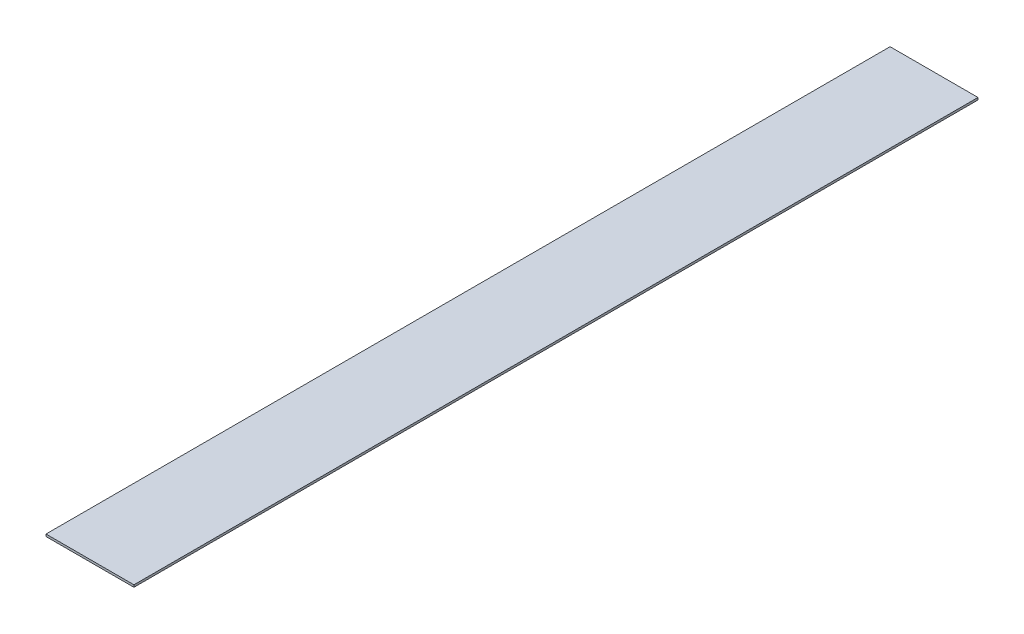
SolidWorks part; units mm, degrees
ref_plane "Спереди" through (0, 0, 0) normal (0, 0, 1) x (1, 0, 0)
ref_plane "Сверху" through (0, 0, 0) normal (0, 1, 0) x (1, 0, 0)
ref_plane "Справа" through (0, 0, 0) normal (1, 0, 0) x (0, 0, -1)
sketch "Эскиз1" plane through (0, 0, 0) normal (0, 0, 1) x (1, 0, 0)
  line L1 (-100, 2.5) -> (100, 2.5)
  line L2 (-100, 2.5) -> (-100, -2.5)
  line L3 (-100, -2.5) -> (100, -2.5)
  line L4 (100, 2.5) -> (100, -2.5)
  line L5 (-100, 2.5) -> (100, -2.5) construction
  line L6 (-100, -2.5) -> (100, 2.5) construction
  point P0 (0, 0)
  dimension "D1" = 5
  dimension "D2" = 200
extrude "Бобышка-Вытянуть1" add sketch "Эскиз1" along normal mid plane 1920
sketch "Эскиз2" plane through (0, -2.5, 0) normal (0, -1, 0) x (1, 0, 0)
  line L0 (0, 960) -> (0, -960) construction
  line L1 (-100, 960) -> (100, 960) construction
  line L2 (-100, -960) -> (100, -960) construction
  line L3 (-100, 0) -> (98.6926, 0) construction
  line L4 (-100, 960) -> (-100, -960) construction
ref_axis "Ось1" through (0, -50, 0) along (0, 1, 0)
